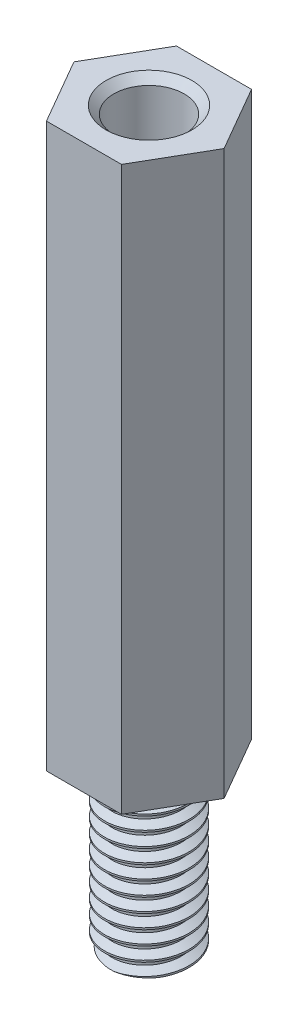
SolidWorks part; units mm, degrees
material "Brass"
ref_plane "Front Plane" through (0, 0, 0) normal (0, 0, 1) x (1, 0, 0)
ref_plane "Top Plane" through (0, 0, 0) normal (0, 1, 0) x (1, 0, 0)
ref_plane "Right Plane" through (0, 0, 0) normal (1, 0, 0) x (0, 0, -1)
sketch "草图1" plane through (0, 0, 0) normal (0, 1, 0) x (1, 0, 0)
  line L1 (2.6674, 0) -> (1.3337, 2.31)
  line L2 (1.3337, 2.31) -> (-1.3337, 2.31)
  line L3 (-1.3337, 2.31) -> (-2.6674, 0)
  line L4 (-2.6674, 0) -> (-1.3337, -2.31)
  line L5 (-1.3337, -2.31) -> (1.3337, -2.31)
  line L6 (1.3337, -2.31) -> (2.6674, 0)
  circle A0 centre (0, 0) radius 2.31 construction
  dimension "D1" = 4.62
extrude "凸台-拉伸1" add sketch "草图1" along normal blind 20
sketch "草图2" plane through (0, 0, 0) normal (0, -1, 0) x (1, 0, 0)
  circle A0 centre (0, 0) radius 1.5
extrude "凸台-拉伸2" add sketch "草图2" along normal blind 5.8
thread "螺纹线1" pitch 0.5 method cut profile "Thread Profile1" start angle 0, offset 0, length 10, pitch 0.5, diameter 3
ref_plane "基准面1" through (-1.5, 0, 0) normal (0, 0, 1) x (-1, 0, 0)
sketch "Thread Profile1" plane through (-1.5, 0, 0) normal (0, 0, 1) x (-1, 0, 0)
  line L0 (0, 0) -> (0, 0.5) construction
  line L11 (0, 0) -> (0, 0.4375)
  line L12 (0, 0.4375) -> (-0.2706, 0.2812)
  line L13 (-0.2706, 0.2812) -> (-0.2706, 0.1562)
  line L15 (-0.2706, 0.1562) -> (0, 0)
  line L17 (-0.2706, 0.2187) -> (0, 0.2187) construction
  point P2 (0, 0)
  dimension "Pitch" = 0.5
  dimension "Profile_Angle" = 60
  dimension "Profile_Land" = 0.125
  dimension "Profile_Height" = 0.2706
sketch "草图9" plane through (0, 20, 0) normal (0, 1, 0) x (1, 0, 0)
  point P0 (0, 0)
hole_wizard "M3 Tapped Hole1" positions "草图9" profile "草图8" tap size "M3" standard "ISO"
sketch "草图8" plane through (0, 20, 0) normal (1, 0, 0) x (0, 0, 1)
  line L0 (0, 0) -> (0, 12.7511)
  line L1 (0, 12.7511) -> (1.25, 12)
  line L2 (1.25, 12) -> (1.25, 0.275)
  line L3 (1.25, 0.275) -> (1.525, 0)
  line L5 (1.525, 0) -> (0, 0)
  line L6 (-1.25, 0.275) -> (-1.525, 0) construction
  line L10 (0, 12.7511) -> (-1.25, 12) construction
  line L11 (0, -6.35) -> (0, 107.95) construction
  dimension "Tap Drill Dia." = 2.5
  dimension "Tap Drill Depth" = 12
  dimension "Near C'Sink Dia." = 3.05
  dimension "Near C'Sink Angle" = 90
  dimension "Drill Angle" = 118
cosmetic thread "孔螺纹线1" parameters "D1"=10, "D2"=3
